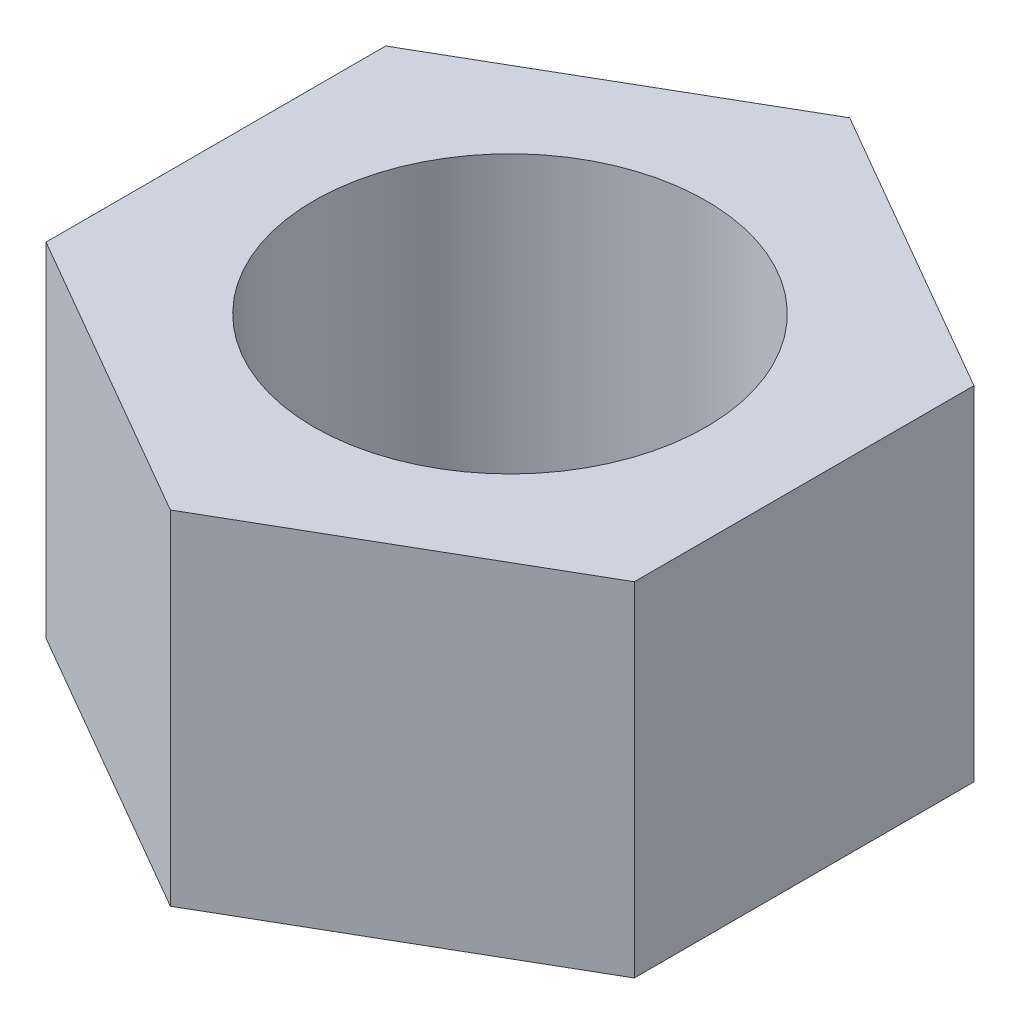
SolidWorks part; units mm, degrees
material "AISI 4130 Steel, normalized at 870C"
ref_plane "Front Plane" through (0, 0, 0) normal (0, 0, 1) x (1, 0, 0)
ref_plane "Top Plane" through (0, 0, 0) normal (0, 1, 0) x (1, 0, 0)
ref_plane "Right Plane" through (0, 0, 0) normal (1, 0, 0) x (0, 0, -1)
sketch "Sketch1" plane through (0, 0, 0) normal (0, 0, 1) x (1, 0, 0)
  line L0 (0, -4.1672) -> (0, 4.1672) construction
  line L1 (7.1438, 0) -> (-7.1438, 0) construction
  line L2 (4.7625, -4.1672) -> (-4.7625, -4.1672) construction
  line L3 (4.7625, -4.1672) -> (4.7625, -3.1089) construction
  point P4 (0, 0)
  point P8 (0, 0)
  point P11 (0, -4.1672)
  dimension "Height" = 8.3344
  dimension "Width" = 14.2875
  dimension "Thread Size" = 9.525
  dimension "Thread Pitch" = 1.0583
sketch "Sketch2" plane through (0, 0, 0) normal (1, 0, 0) x (0, 0, -1)
  line L0 (0, -4.1672) -> (0, 4.1672) construction
  line L1 (3.048, -1.9542) -> (-3.048, -1.9542)
  line L2 (3.048, -1.9542) -> (3.048, 4.1672)
  line L3 (3.048, 4.1672) -> (-3.048, 4.1672)
  line L4 (-3.048, -1.9542) -> (-3.048, 4.1672)
  line L5 (3.048, -1.9542) -> (-3.048, 4.1672) construction
  line L6 (3.048, 4.1672) -> (-3.048, -1.9542) construction
  point P0 (0, 1.1065)
  point P7 (0, 4.1672)
  dimension "Minimum Slot Width" = 6.096
  dimension "Minimum Slot Depth" = 6.1214
sketch "Sketch11" plane through (0, 0, 0) normal (0, 1, 0) x (1, 0, 0)
  line L1 (0, 8.2489) -> (-7.1438, 4.1244)
  line L2 (-7.1438, 4.1244) -> (-7.1438, -4.1244)
  line L3 (-7.1438, -4.1244) -> (0, -8.2489)
  line L4 (0, -8.2489) -> (7.1438, -4.1244)
  line L5 (7.1438, -4.1244) -> (7.1438, 4.1244)
  line L6 (7.1438, 4.1244) -> (0, 8.2489)
  circle A0 centre (0, 0) radius 7.1438 construction
  circle A1 centre (0, 0) radius 4.7625
  point P19 (0, -4.7625)
extrude "Boss-Extrude1" add sketch "Sketch11" along normal up to vertex (4.1672 mm away) and the other way up to vertex (4.1672 mm away) up to point (0, 4.1672, 0) other way up to point (0, -4.1672, 0)
fillet "Fillet1" [suppressed] radius 0.4286
sketch "Sketch3" plane through (0, 0, 0) normal (1, 0, 0) x (0, 0, -1)
  line L1 (4.1244, 4.1672) -> (8.2489, 4.1672) construction
  line L2 (6.4294, -4.1672) -> (8.2489, -3.1167)
  line L3 (4.1244, -4.1672) -> (8.2489, -4.1672) construction
  line L4 (8.2489, 4.1672) -> (8.2489, -4.1672) construction
  line L5 (8.2489, -3.1167) -> (8.2489, -4.1672)
  line L7 (6.7151, 4.1672) -> (8.2489, 3.2817)
  line L8 (8.2489, 3.2817) -> (8.2489, 4.1672)
  line L10 (6.4294, -4.1672) -> (8.2489, -4.1672)
  line L12 (6.7151, 0) -> (7.1438, 0) construction
  line L16 (6.7151, 4.1672) -> (8.2489, 4.1672)
  line L21 (4.7625, -4.1672) -> (4.7625, -3.9291)
  line L22 (-4.1244, -4.1672) -> (4.1244, -4.1672) construction
  line L24 (5.0006, -4.1672) -> (4.7625, -4.1672)
  line L25 (4.7625, -3.9291) -> (5.0006, -4.1672)
  line L26 (4.7625, 4.1672) -> (4.7625, 3.9291)
  line L27 (4.7625, 4.1672) -> (5.0006, 4.1672)
  line L28 (5.0006, 4.1672) -> (4.7625, 3.9291)
  line L29 (3.048, 4.1672) -> (-3.048, 4.1672) construction
  line L30 (5.0006, 0) -> (5.4293, 0) construction
  line L31 (6.2865, 0) -> (6.7151, 0) construction
  line L32 (5.4293, 0) -> (5.8579, 0) construction
  line L33 (5.8579, 0) -> (6.2865, 0) construction
  point P0 (6.7151, 4.1672)
  point P1 (7.1438, 0)
  point P14 (4.7625, 0)
  point P36 (7.1438, -4.1672)
  point P44 (6.9294, 0)
  dimension "D2" = 30
  dimension "D5" = 0.2381
  dimension "D7" = 0.7144
  dimension "D1" = 30
revolve "Cut-Revolve2" [suppressed] cut sketch "Sketch3" angle 360 about L0
sketch "Sketch15" [suppressed] plane through (15.4781, 0, 17.1852) normal (0.5, 0, -0.866) x (-0.866, 0, -0.5)
  line L0 (21.997, 3.9197) -> (21.997, 2.0011) construction
  line L1 (21.997, -1.8361) -> (21.997, 0.0825) construction
  line L2 (21.997, 0.0825) -> (21.997, 2.0011) construction
  line L3 (21.997, -1.8361) -> (21.997, -3.7547) construction
  line L6 (20.8893, 0.0825) -> (21.4432, -0.8768)
  line L7 (21.4432, -0.8768) -> (22.5509, -0.8768)
  line L8 (22.5509, -0.8768) -> (23.1048, 0.0825)
  line L9 (23.1048, 0.0825) -> (22.5509, 1.0418)
  line L10 (22.5509, 1.0418) -> (21.4432, 1.0418)
  line L11 (21.4432, 1.0418) -> (20.8893, 0.0825)
  circle A0 centre (21.997, 0.0825) radius 0.9593 construction
  spline S4 degree 3 poles (17.8726, 3.2817) (18.546, 3.4761) (19.2244, 3.6363) (20.5953, 3.8583) (21.2879, 3.9193) (22.3398, 3.9199) (22.6921, 3.905) (23.389, 3.8469) (23.7351, 3.8037) (24.7673, 3.6369) (25.4472, 3.4763) (26.1215, 3.2817) knots 0 0 0 0 0.25 0.25 0.5 0.5 0.625 0.625 0.75 0.75 1 1 1 1 construction
  spline S5 degree 3 poles (26.1215, -3.1167) (25.448, -3.3111) (24.7697, -3.4713) (23.3988, -3.6933) (22.7062, -3.7543) (21.6543, -3.755) (21.302, -3.74) (20.6051, -3.6819) (20.259, -3.6387) (19.2268, -3.472) (18.5469, -3.3113) (17.8726, -3.1167) knots 0 0 0 0 0.25 0.25 0.5 0.5 0.625 0.625 0.75 0.75 1 1 1 1 construction
  point P1 (21.997, 1.0418)
  point P6 (21.997, 0)
extrude "Cut-Extrude2" [suppressed] cut sketch "Sketch15" along normal blind 0.1905
sketch "Sketch18" [suppressed] plane through (0, 4.1672, 0) normal (0, 1, 0) x (1, 0, 0)
  line L0 (0, 0) -> (0, -6.7151) construction
  line L1 (0, 0) -> (-4.1421, -4.1421) construction
  line L2 (0, 0) -> (-1.5161, -5.6583) construction
  line L3 (-6.7151, 0) -> (-6.3722, 0) construction
  line L4 (-6.3722, 0) -> (-6.0293, 0) construction
  line L5 (-6.0293, 0) -> (-5.6864, 0) construction
  line L6 (-5.6864, 0) -> (-5.3435, 0) construction
  line L7 (-5.3435, 0) -> (-5.0006, 0) construction
  line L8 (0, 0) -> (-3.5719, -6.1867) construction
  line L9 (-7.1437, -4.1244) -> (0, -8.2489) construction
  circle A0 centre (0, 0) radius 6.7151 construction
  circle A1 centre (0, 0) radius 5.0006 construction
  arc A2 (-4.1421, -4.1421) -> (-1.5161, -5.6583) centre (0, 0) ccw construction
  arc A3 (-4.2634, -4.2634) -> (-1.5605, -5.8239) centre (0, 0) ccw
  arc A4 (-4.0209, -4.0209) -> (-1.4718, -5.4927) centre (0, 0) ccw
  arc A5 (-4.0209, -4.0209) -> (-4.2634, -4.2634) centre (-4.1421, -4.1421) ccw
  arc A6 (-1.5605, -5.8239) -> (-1.4718, -5.4927) centre (-1.5161, -5.6583) ccw
  arc A7 (4.1421, -4.1421) -> (1.5161, -5.6583) centre (0, 0) cw construction
  arc A8 (4.2634, -4.2634) -> (1.5605, -5.8239) centre (0, 0) cw
  arc A9 (4.0209, -4.0209) -> (1.4718, -5.4927) centre (0, 0) cw
  arc A10 (4.0209, -4.0209) -> (4.2634, -4.2634) centre (4.1421, -4.1421) cw
  arc A11 (1.5605, -5.8239) -> (1.4718, -5.4927) centre (1.5161, -5.6583) cw
  point P18 (-2.9289, -5.0731)
  point P30 (2.9289, -5.0731)
  dimension "D1" = 30
extrude "Cut-Extrude3" [suppressed] cut sketch "Sketch18" against normal blind 0.2381
sketch "Sketch5" [suppressed] plane through (0, 0, 0) normal (0, 1, 0) x (1, 0, 0)
  circle A1 centre (0, 0) radius 4.7625 construction
  point P0 (0, -4.7625)
sketch "Sketch6" [suppressed] plane through (0, 0, 0) normal (0, 0, 1) x (1, 0, 0)
  line L0 (4.7625, 4.1672) -> (4.7625, -4.1672)
  line L2 (0, -4.1672) -> (7.1438, -4.1672) construction
  line L3 (4.7625, -4.1672) -> (0, -4.1672)
  line L4 (0, -4.1672) -> (0, 4.1672)
  line L5 (0, -4.1672) -> (0, 4.1672) construction
  line L6 (0, 4.1672) -> (4.7625, 4.1672)
revolve "Revolve2" [suppressed] add sketch "Sketch6" angle 360 about L4
sketch "Sketch7" [suppressed] plane through (0, -4.1672, 0) normal (0, -1, 0) x (1, 0, 0)
  circle A2 centre (0, 0) radius 4.7625
  circle A3 centre (0, 0) radius 4.7625
  dimension "D1" = 0
curve "Helix/Spiral1" [suppressed] pitch 1.0583 height 8.3344 turns 7.875
sketch "Sketch8" [suppressed] plane through (0, 0, 0) normal (0, 0, 1) x (1, 0, 0)
  line L0 (4.8771, -4.101) -> (3.9605, -4.6302) construction
  line L1 (3.9605, -4.6302) -> (4.8771, -5.1594) construction
  line L2 (4.8771, -5.1594) -> (4.8771, -4.101) construction
  line L3 (4.0751, -4.5641) -> (4.0751, -4.6964)
  line L4 (4.7625, -4.1672) -> (4.7625, -5.0932) construction
  line L5 (4.7625, -4.6302) -> (4.8771, -4.6302) construction
  line L6 (3.9605, -4.6302) -> (4.0751, -4.6302) construction
  line L7 (4.8198, -4.6302) -> (4.8198, -5.1263) construction
  line L8 (4.0751, -4.5641) -> (4.8771, -4.101)
  line L9 (4.8771, -4.101) -> (4.8198, -5.1263)
  line L10 (4.0751, -4.6964) -> (4.8198, -5.1263)
  dimension "D1" = 1.0583
  dimension "D2" = 0.1323
sweep "Cut-Sweep1" [suppressed] cut profiles "Sketch8" path "Helix/Spiral1"
sketch "Sketch9" [suppressed] plane through (0, 0, 0) normal (0, 0, 1) x (1, 0, 0)
  line L0 (0, 0.5953) -> (0, -4.1672)
  line L1 (0, 0.5953) -> (0, 0.8334)
  line L2 (0, -4.1672) -> (4.7625, -4.1672)
  line L3 (4.7625, -4.1672) -> (5.0006, -4.1672)
  line L4 (5.0006, -4.1672) -> (0, 0.8334)
  dimension "D1" = 0.2381
revolve "Revolve3" [suppressed] add sketch "Sketch9" angle 360 about L0
sketch "Sketch14" [suppressed] plane through (0, 0, 0) normal (0, 0, 1) x (1, 0, 0)
  line L0 (5.0006, 4.1672) -> (0, 4.1672)
  line L1 (0, 4.1672) -> (0, -0.8334)
  line L2 (0, -0.8334) -> (5.0006, 4.1672)
revolve "Revolve4" [suppressed] add sketch "Sketch14" angle 360 about L1
sketch "Sketch10" [suppressed] plane through (0, -4.1672, 0) normal (0, -1, 0) x (1, 0, 0)
  circle A0 centre (0, 0) radius 5.0006 construction
  circle A1 centre (0, 0) radius 5.0006
extrude "Boss-Extrude2" [suppressed] add sketch "Sketch10" against normal up to surface (8.3344 mm away) up to face at (0, 4.1672, 0)
combine bodies "Combine1" [suppressed] operation type subtract main body 110 bodies to subtract 120
move or copy body "Body-Move/Copy1" [suppressed] bodies to move or copy 104 parameters "D1"=0, "D2"=0, "D3"=0
move or copy body "Body-Move/Copy2" [suppressed] bodies to move or copy 124 parameters "D1"=0, "D2"=0, "D3"=0
equation "\"D5@Sketch3\"=\"Thread Size@Sketch1\"*.025"
equation "\"D4@Helix/Spiral1\" = \"Thread Pitch@Sketch1\""
equation "\"D3@Helix/Spiral1\" = \"Height@Sketch1\""
equation "\"D1@Sketch8\" = \"Thread Pitch@Sketch1\""
equation "\"D2@Sketch8\" = \"Thread Pitch@Sketch1\" / 8"
equation "\"D1@Sketch9\"=\"Thread Size@Sketch1\" * .025"
equation "\"D1@Fillet1\"=\"Width@Sketch1\" * .03"
equation "\"D7@Sketch3\"=\"Width@Sketch1\"*.05"
equation "\"D1@Cut-Extrude2\" =  (  ( \"Width@Sketch1\" - \"Thread Size@Sketch1\" / 2 )  * .02 ) "
equation "\"D1@Cut-Extrude3\"=((\"width@sketch1\"-\"Thread Size@sketch1\"/2)*.025)"
